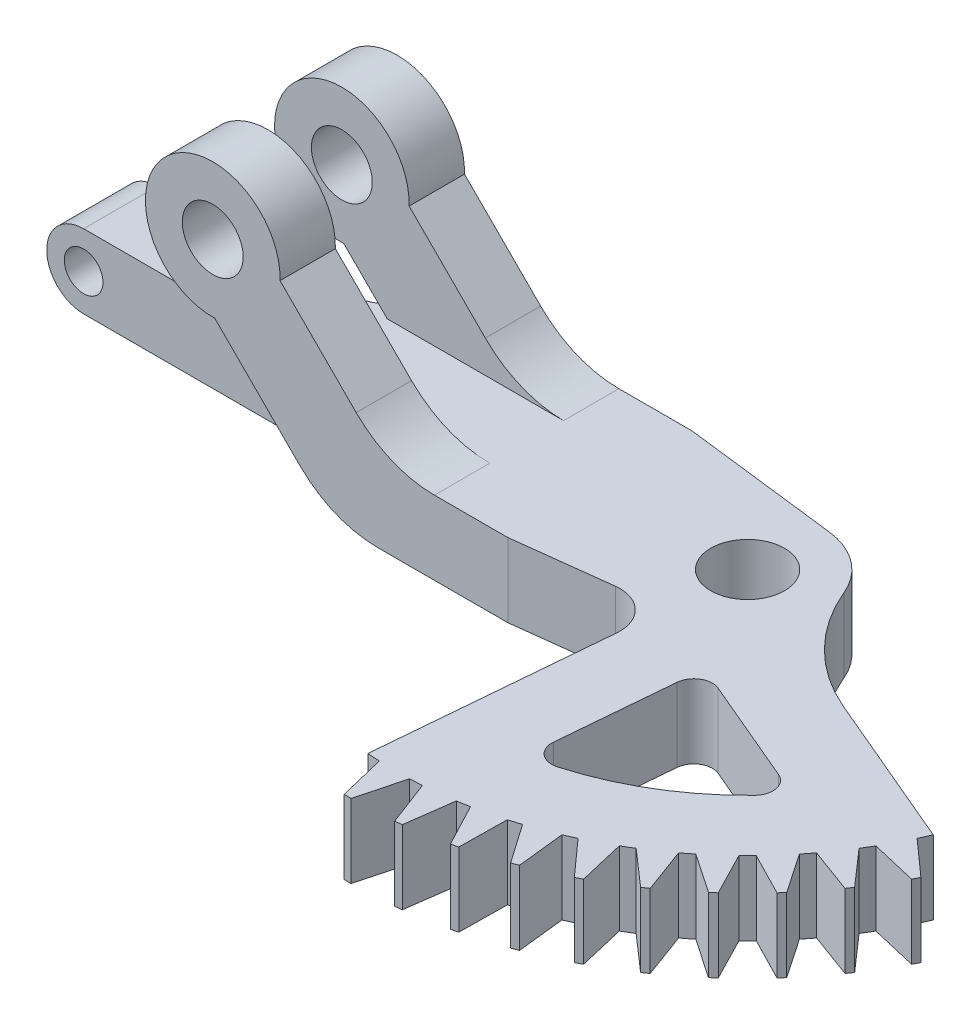
SolidWorks part; units mm, degrees
ref_plane "Front Plane" through (0, 0, 0) normal (0, 0, 1) x (1, 0, 0)
ref_plane "Top Plane" through (0, 0, 0) normal (0, 1, 0) x (1, 0, 0)
ref_plane "Right Plane" through (0, 0, 0) normal (1, 0, 0) x (0, 0, -1)
sketch "Sketch1" plane through (0, 0, 0) normal (0, 0, 1) x (1, 0, 0)
  line L0 (6.4645, -10) -> (16, -10)
  line L1 (16, -10) -> (16, -6)
  line L2 (16, -6) -> (9.5355, -6)
  line L3 (9.5355, -6) -> (3.6483, -0.1127)
  line L4 (6.4645, -10) -> (0.1127, -3.6483)
  line L5 (0, 0) -> (14.0151, -14.0151) construction
  line L6 (0, 0) -> (0, -20.1214) construction
  circle A0 centre (0, 0) radius 1.65
  arc A1 (3.6483, -0.1127) -> (0.1127, -3.6483) centre (0, 0) ccw
  arc A2 (2.5809, -2.5809) -> (3.6483, -0.1127) centre (0, 0) ccw construction
  arc A3 (0.1127, -3.6483) -> (2.5809, -2.5809) centre (0, 0) ccw construction
  circle A4 centre (0, 0) radius 3.65 construction
  point P5 (4, 0)
  dimension "D1" = 3.3
  dimension "D3" = 4
  dimension "D4" = 5
  dimension "D5" = 16
  dimension "D6" = 6
  dimension "D7" = 45
  dimension "D2" = 2
extrude "Boss-Extrude1" add sketch "Sketch1" along normal mid plane 10
sketch "Sketch3" plane through (0, -10, 0) normal (0, -1, 0) x (1, 0, 0)
  line L0 (-3.65, -5) -> (3.65, -5) construction
  line L1 (3.65, 5) -> (-3.65, 5) construction
  line L4 (6.4645, -5) -> (6.4645, 5) construction
  line L6 (-3.65, -5) -> (3.65, -5) construction
  line L7 (3.65, 5) -> (-3.65, 5) construction
  line L8 (6.4645, 2) -> (-3.65, 2)
  line L9 (-3.65, 2) -> (-3.65, -2)
  line L10 (6.4645, -2) -> (6.4645, 2)
  line L11 (-3.65, -2) -> (6.4645, -2)
  line L12 (0, 0) -> (-8.9484, 0) construction
  line L13 (6.4645, 2) -> (6.4645, 5) construction
  line L14 (6.4645, -5) -> (6.4645, -2) construction
  dimension "D1" = 4
extrude "Cut-Extrude1" cut sketch "Sketch3" against normal through all
sketch "Sketch4" plane through (0, -10, 0) normal (0, -1, 0) x (1, 0, 0)
  line L0 (16, 5) -> (16, -5) construction
  line L1 (16, 5) -> (16, -5)
  line L2 (0, 0) -> (22, 0) construction
  line L4 (16, -5) -> (21.1955, -4.3696)
  line L5 (24, -40.1964) -> (24, 20.3832) construction
  line L8 (20, 0) -> (22, 0) construction
  line L9 (24, 0) -> (21.8146, -24.9797) construction
  line L10 (23.4288, -6.5294) -> (22.1262, -21.4182) construction
  line L11 (33.0191, -3.8284) -> (43.7909, -8.4007) construction
  line L12 (26, 0) -> (28, 0) construction
  line L13 (22, 0) -> (24, 0) construction
  line L14 (21.1955, -4.3696) -> (24.4818, -3.9709)
  line L16 (24, 0) -> (26, 0) construction
  line L17 (16, 5) -> (21.1955, 4.3696)
  line L18 (23.4288, 6.5294) -> (22.1262, 21.4182)
  line L19 (33.0191, 3.8284) -> (43.7909, 8.4007)
  line L20 (16, 0) -> (20, 0) construction
  line L21 (26, 0) -> (33.4439, 0) construction
  line L22 (24, 0) -> (26, 0) construction
  line L23 (22, 0) -> (24, 0) construction
  circle A0 centre (24, 0) radius 2
  arc A1 (27.6933, 1.5362) -> (28, 0) centre (24, 0) ccw construction
  arc A2 (20, 0) -> (24.4818, -3.9709) centre (24, 0) ccw construction
  arc A3 (20.318, 1.5629) -> (20, 0) centre (24, 0) ccw construction
  circle A4 centre (24, 0) radius 4 construction
  arc A5 (24, -21.5) -> (43.7909, -8.4007) centre (24, 0) ccw construction
  arc A7 (24, 4) -> (20.318, 1.5629) centre (24, 0) ccw construction
  arc A8 (24.4818, -3.9709) -> (27.6933, -1.5362) centre (24, 0) ccw
  arc A10 (33.0191, -3.8284) -> (27.6933, 1.5362) centre (36.9264, 5.3767) cw construction
  arc A12 (23.4288, -6.5294) -> (21.1955, -4.3696) centre (21.4364, -6.3551) ccw construction
  arc A13 (28, 0) -> (27.6933, -1.5362) centre (24, 0) ccw construction
  arc A14 (24, 2) -> (22, 0) centre (24, 0) ccw construction
  arc A15 (26, 0) -> (24, 2) centre (24, 0) ccw construction
  circle A16 centre (24, 0) radius 2 construction
  arc A17 (23.4288, 6.5294) -> (21.1955, 4.3696) centre (21.4364, 6.3551) cw
  arc A18 (33.0191, 3.8284) -> (27.6933, -1.5362) centre (36.9264, -5.3767) ccw
  arc A19 (22.1262, 21.4182) -> (43.7909, 8.4007) centre (24, 0) cw
  arc A20 (27.6933, -1.5362) -> (24, 4) centre (24, 0) ccw construction
  arc A21 (22.1262, -21.4182) -> (24, -21.5) centre (24, 0) ccw construction
  point P10 (28, 0)
  point P16 (25.9126, 0.5847)
  dimension "D1" = 4
  dimension "D4" = 43
  dimension "D5" = 10
  dimension "D6" = 2
  dimension "D2" = 8
  dimension "D7" = 5
  dimension "D8" = 67
  dimension "D3" = 2
extrude "Boss-Extrude2" add sketch "Sketch4" against normal up to surface (4 mm away) up to face at (12.7678, -6, 0)
sketch "Sketch5" plane through (0, 0, 0) normal (0, 0, 1) x (1, 0, 0)
  line L2 (6.4645, -10) -> (-10, -10)
  line L3 (9.5355, -6) -> (-10, -6)
  line L4 (16, -6) -> (9.5355, -6) construction
  line L5 (16, -6) -> (9.5355, -6)
  line L6 (6.4645, -10) -> (16, -10) construction
  line L7 (6.4645, -10) -> (16, -10)
  line L8 (16, -10) -> (16, -6)
  arc A2 (-10, -6) -> (-10, -10) centre (-10, -8) ccw
  circle A3 centre (-10, -8) radius 1.05
  arc A4 (-10, -10) -> (-10, -6) centre (-10, -8) ccw construction
  dimension "D2" = 2.1
  dimension "D1" = 10
extrude "Boss-Extrude3" add sketch "Sketch5" along normal mid plane 4
sketch "Sketch6" plane through (0, -10, 0) normal (0, -1, 0) x (1, 0, 0)
  line L0 (33.0191, 3.8284) -> (43.7909, 8.4007) construction
  line L1 (41.4896, 7.4239) -> (43.7909, 8.4007) construction
  line L2 (22.344, 18.9277) -> (23.4288, 6.5294) construction
  line L4 (33.0191, 3.8284) -> (41.4896, 7.4239) construction
  line L6 (22.1262, 21.4182) -> (23.4288, 6.5294) construction
  line L7 (22.1262, 21.4182) -> (22.344, 18.9277) construction
  line L8 (24, 0) -> (41.738, 6.809) construction
  line L9 (24, 0) -> (51.2405, 9.3796) construction
  line L11 (24, 0) -> (43.4856, 9.0863) construction
  line L12 (41.738, 6.809) -> (46.8491, 8.7709) construction
  line L13 (24, 0) -> (47.3642, 11.9047) construction
  line L16 (24, 0) -> (51.5186, 15.2538) construction
  line L19 (41.2198, 8.0297) -> (43.1566, 9.7608)
  line L20 (41.4896, 7.4239) -> (44.072, 7.7049)
  arc A0 (43.7909, 8.4007) -> (22.1262, 21.4182) centre (24, 0) ccw construction
  arc A1 (43.4856, 9.0863) -> (43.1566, 9.7608) centre (24, 0) ccw
  arc A2 (41.4896, 7.4239) -> (41.2198, 8.0297) centre (24, 0) ccw
  arc A3 (22.344, 18.9277) -> (41.9649, 6.1858) centre (24, 0) ccw construction
  arc A4 (44.072, 7.7049) -> (43.7909, 8.4007) centre (24, 0) ccw
  arc A5 (41.2198, 8.0297) -> (40.9291, 8.6258) centre (24, 0) ccw construction
  circle A6 centre (24, 0) radius 19 construction
  arc A7 (41.738, 6.809) -> (41.4896, 7.4239) centre (24, 0) ccw construction
  arc A8 (41.9649, 6.1858) -> (41.738, 6.809) centre (24, 0) ccw construction
  arc A9 (43.1566, 9.7608) -> (42.8043, 10.4234) centre (24, 0) ccw construction
  arc A10 (44.3286, 6.9997) -> (44.072, 7.7049) centre (24, 0) ccw construction
  arc A11 (42.8043, 10.4234) -> (22.1262, 21.4182) centre (24, 0) ccw construction
  arc A12 (43.7909, 8.4007) -> (43.4856, 9.0863) centre (24, 0) ccw
  arc A13 (40.6178, 9.2114) -> (22.344, 18.9277) centre (24, 0) ccw construction
  arc A14 (40.9291, 8.6258) -> (40.6178, 9.2114) centre (24, 0) ccw construction
  dimension "D3" = 2.5
  dimension "D1" = 2
  dimension "D2" = 2
  dimension "D4" = 4
  dimension "D5" = 4
  dimension "D6" = 2
extrude "Cut-Extrude2" cut sketch "Sketch6" against normal up to next (4 mm away)
pattern_circular "CirPattern1" count 11 every 7 about axis through (24, -10, 0) along (0, -1, 0) of "Cut-Extrude2"
sketch "Sketch7" plane through (0, -6, 0) normal (0, 1, 0) x (1, 0, 0)
  line L0 (6.4645, -2) -> (3.6483, -2) construction
  line L1 (3.6483, 2) -> (6.4645, 2) construction
  line L2 (9.5355, -5) -> (9.5355, 5) construction
  line L3 (6.4645, 2) -> (6.4645, -2) construction
  line L4 (9.5355, -2) -> (6.4645, -2)
  line L5 (6.4645, 2) -> (9.5355, 2)
  line L6 (9.5355, -2) -> (9.5355, 2)
  line L7 (6.4645, 2) -> (6.4645, -2)
  line L8 (3.6483, 2) -> (6.4645, 2) construction
  line L9 (6.4645, -2) -> (3.6483, -2) construction
  line L10 (9.5355, -5) -> (9.5355, -2) construction
  line L11 (9.5355, 2) -> (9.5355, 5) construction
extrude "Cut-Extrude3" cut sketch "Sketch7" along normal blind 4
fillet "Fillet1" radius 6 4 edges at (9.5355, -6, 3.5) (9.5355, -6, -3.5) (6.4645, -10, -3.5) (6.4645, -10, 3.5)
fillet "Fillet2" radius 2 4 edges at (3.5858, -7.1213, -2) (3.5858, -7.1213, 2) (6.6536, -9.5433, -2) (6.6536, -9.5433, 2)
sketch "Sketch8" plane through (0, -6, 0) normal (0, 1, 0) x (1, 0, 0)
  line L0 (23.4288, -6.5294) -> (22.344, -18.9277) construction
  line L1 (41.4896, -7.4239) -> (33.0191, -3.8284) construction
  line L2 (23.4288, -6.5294) -> (22.344, -18.9277) construction
  line L3 (41.4896, -7.4239) -> (33.0191, -3.8284) construction
  line L4 (39.9267, -11.1059) -> (39.5347, -10.9395) construction
  line L5 (27.385, -7.2043) -> (26.8451, -13.3756)
  line L6 (27.4135, -6.878) -> (26.3288, -19.2763) construction
  line L7 (39.9267, -11.1059) -> (31.4561, -7.5104) construction
  line L8 (27.5686, -5.1053) -> (27.5049, -5.8332) construction
  line L9 (26.3659, -18.8521) -> (26.3288, -19.2763)
  line L10 (26.7248, -14.7504) -> (26.3659, -18.8521) construction
  line L11 (34.4742, -8.7915) -> (28.7719, -6.371)
  line L12 (39.5347, -10.9395) -> (35.7447, -9.3308) construction
  arc A0 (33.5, -16.4545) -> (34.0685, -16.1129) centre (24, 0) ccw construction
  arc A1 (26.3659, -18.8521) -> (39.5347, -10.9395) centre (24, 0) ccw construction
  arc A2 (28.1156, -14.4243) -> (34.8038, -10.4057) centre (24, 0) ccw
  arc A3 (33.5, -16.4545) -> (34.0685, -16.1129) centre (24, 0) ccw construction
  arc A4 (31.5, -12.9904) -> (31.9488, -12.7207) centre (24, 0) ccw construction
  arc A5 (28.7719, -6.371) -> (27.385, -7.2043) centre (28.3812, -7.2915) ccw
  arc A6 (28.1156, -14.4243) -> (26.8451, -13.3756) centre (27.8413, -13.4627) cw
  arc A7 (34.8038, -10.4057) -> (34.4742, -8.7915) centre (34.0835, -9.712) ccw
  point P14 (27.5686, -5.1053)
  dimension "D2" = 1
  dimension "D1" = 4
extrude "Cut-Extrude4" cut sketch "Sketch8" against normal up to next contours A2 A7 L11 A5 L5 A6 region at (30.2122, -6, 10.3388)
